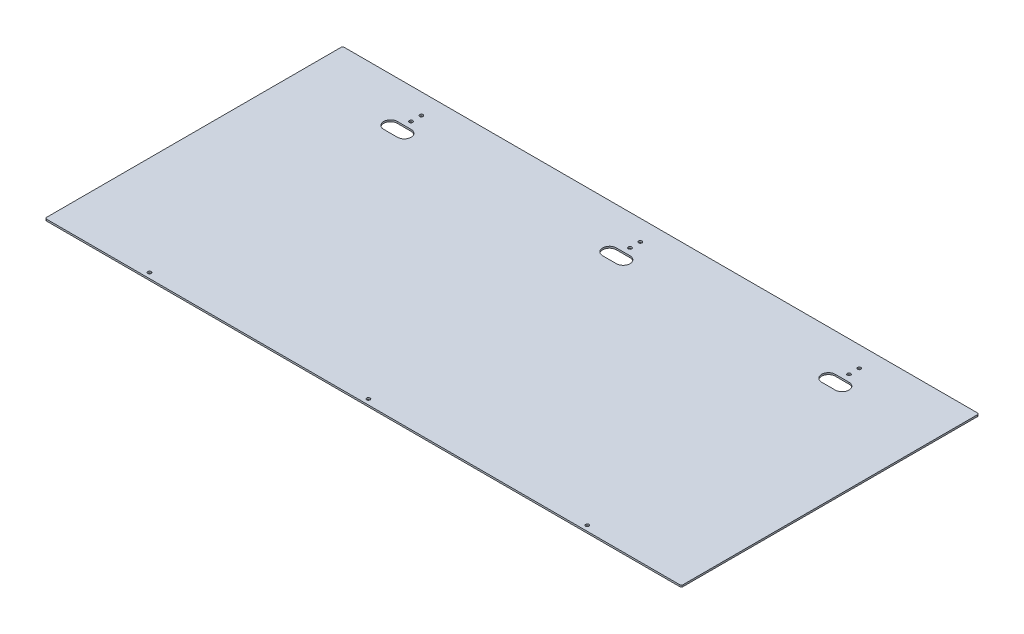
SolidWorks part; units mm, degrees
material "PE High Density"
ref_plane "Front Plane" through (0, 0, 0) normal (0, 0, 1) x (1, 0, 0)
ref_plane "Top Plane" through (0, 0, 0) normal (0, 1, 0) x (1, 0, 0)
ref_plane "Right Plane" through (0, 0, 0) normal (1, 0, 0) x (0, 0, -1)
sketch "Sketch1" plane through (0, 0, 0) normal (0, 1, 0) x (1, 0, 0)
  line L1 (-587.375, -276.225) -> (587.375, -276.225)
  line L2 (-590.55, -273.05) -> (-590.55, 273.05)
  line L3 (-587.375, 276.225) -> (587.375, 276.225)
  line L4 (590.55, -273.05) -> (590.55, 273.05)
  line L5 (-590.55, -276.225) -> (590.55, 276.225) construction
  line L6 (-590.55, 276.225) -> (590.55, -276.225) construction
  arc A0 (587.375, 276.225) -> (590.55, 273.05) centre (587.375, 273.05) cw
  arc A1 (587.375, -276.225) -> (590.55, -273.05) centre (587.375, -273.05) ccw
  arc A2 (-587.375, -276.225) -> (-590.55, -273.05) centre (-587.375, -273.05) cw
  arc A3 (-590.55, 273.05) -> (-587.375, 276.225) centre (-587.375, 273.05) cw
  point P0 (0, 0)
  dimension "D3" = 3.175
  dimension "D1" = 1181.1
  dimension "D2" = 552.45
extrude "Boss-Extrude1" add sketch "Sketch1" along normal blind 3.175
sketch "Sketch2" plane through (0, 3.175, 0) normal (0, 1, 0) x (1, 0, 0)
  line L0 (587.375, 276.225) -> (-587.375, 276.225) construction
  line L1 (-590.55, 273.05) -> (-590.55, -273.05) construction
  line L2 (587.375, 276.225) -> (-587.375, 276.225) construction
  line L3 (590.55, -273.05) -> (590.55, 273.05) construction
  line L4 (-587.375, -276.225) -> (587.375, -276.225) construction
  point P0 (-406.4, 219.075)
  point P5 (0, 219.075)
  point P7 (406.4, 219.075)
  point P20 (-406.4, 238.125)
  point P21 (406.4, -266.573)
  point P29 (0, -266.573)
  point P31 (-406.4, -266.573)
  point P35 (0, 238.125)
  point P51 (406.4, 238.125)
  dimension "D1" = 57.15
  dimension "D2" = 9.652
  dimension "D3" = 184.15
  dimension "D4" = 406.4
  dimension "D5" = 406.4
  dimension "D6" = 406.4
  dimension "D7" = 184.15
  dimension "D9" = 406.4
  dimension "D10" = 9.652
  dimension "D13" = 38.1
  dimension "D14" = 184.15
hole_wizard "1/4 (0.25) Diameter Hole1" positions "Sketch3" profile "Sketch4" hole size "1/4" standard "ANSI Inch" end condition through all
sketch "Sketch3" plane through (0, 3.175, 0) normal (0, 1, 0) x (1, 0, 0)
  point P0 (-406.4, 219.075)
  point P6 (0, 219.075)
  point P12 (406.4, 219.075)
  point P54 (-406.4, -266.573)
  point P60 (0, -266.573)
  point P66 (406.4, -266.573)
  point P69 (-406.4, 238.125)
  point P75 (0, 238.125)
  point P81 (406.4, 238.125)
sketch "Sketch4" plane through (-406.4, 3.175, -219.075) normal (1, 0, 0) x (0, 0, 1)
  line L0 (0, 0) -> (0, 3.175)
  line L1 (0, 3.175) -> (3.175, 3.175)
  line L2 (3.175, 3.175) -> (3.175, 0)
  line L5 (3.175, 0) -> (0, 0)
  line L11 (0, -6.35) -> (0, 107.95) construction
  dimension "Thru Hole Dia." = 6.35
  dimension "Thru Hole Depth" = 3.175
sketch "Sketch5" plane through (0, 3.175, 0) normal (0, 1, 0) x (1, 0, 0)
  line L0 (-590.55, 273.05) -> (-590.55, -273.05) construction
  line L3 (590.55, -273.05) -> (590.55, 273.05) construction
  line L33 (587.375, 276.225) -> (-587.375, 276.225) construction
  line L36 (-419.1, 193.675) -> (-393.7, 193.675) construction
  line L37 (-419.1, 206.375) -> (-393.7, 206.375)
  line L38 (-419.1, 180.975) -> (-393.7, 180.975)
  line L42 (-12.7, 193.675) -> (12.7, 193.675) construction
  line L43 (-12.7, 206.375) -> (12.7, 206.375)
  line L44 (-12.7, 180.975) -> (12.7, 180.975)
  line L48 (393.7, 193.675) -> (419.1, 193.675) construction
  line L49 (393.7, 206.375) -> (419.1, 206.375)
  line L50 (393.7, 180.975) -> (419.1, 180.975)
  line L51 (-403.225, 219.075) -> (-406.4, 219.075) construction
  circle A2 centre (0, 219.075) radius 3.175 construction
  arc A22 (-419.1, 206.375) -> (-419.1, 180.975) centre (-419.1, 193.675) ccw
  arc A23 (-393.7, 180.975) -> (-393.7, 206.375) centre (-393.7, 193.675) ccw
  arc A26 (-12.7, 206.375) -> (-12.7, 180.975) centre (-12.7, 193.675) ccw
  arc A27 (12.7, 180.975) -> (12.7, 206.375) centre (12.7, 193.675) ccw
  arc A30 (393.7, 206.375) -> (393.7, 180.975) centre (393.7, 193.675) ccw
  arc A31 (419.1, 180.975) -> (419.1, 206.375) centre (419.1, 193.675) ccw
  circle A32 centre (-406.4, 219.075) radius 3.175 construction
  circle A33 centre (406.4, 219.075) radius 3.175 construction
  point P95 (-406.4, 193.675)
  point P109 (0, 193.675)
  point P123 (406.4, 193.675)
  dimension "D2" = 184.15
  dimension "D3" = 406.4
  dimension "D4" = 406.4
  dimension "D5" = 184.15
  dimension "D6" = 12.7
  dimension "D7" = 12.7
  dimension "D10" = 12.7
  dimension "D11" = 25.4
  dimension "D12" = 25.4
extrude "Cut-Extrude1" cut sketch "Sketch5" against normal through all
